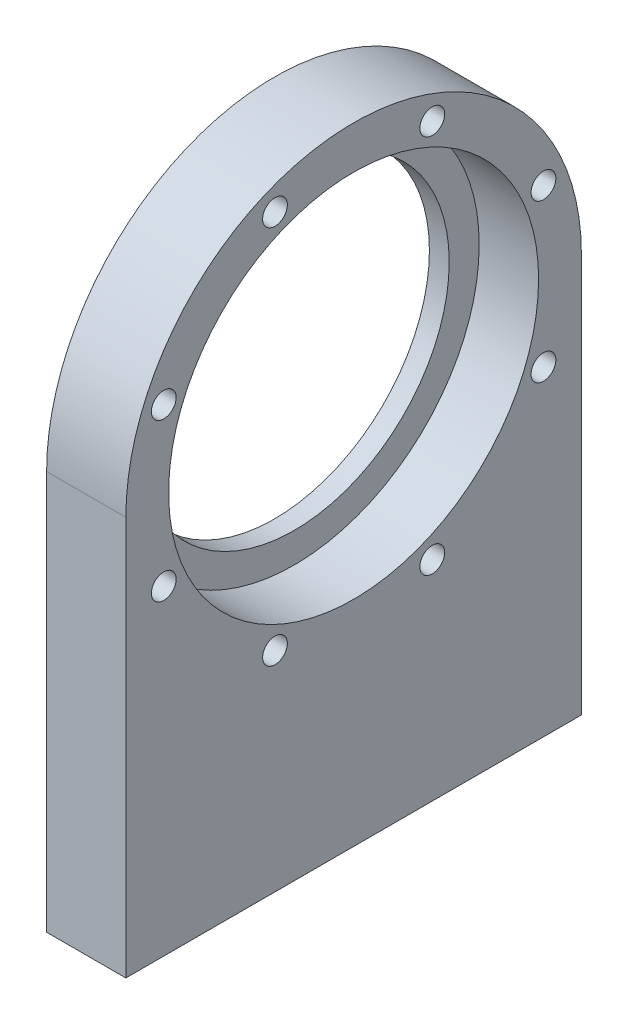
SolidWorks part; units mm, degrees
material "3d打印 35%"
ref_plane "前视基准面" through (0, 0, 0) normal (0, 0, 1) x (1, 0, 0)
ref_plane "上视基准面" through (0, 0, 0) normal (0, 1, 0) x (1, 0, 0)
ref_plane "右视基准面" through (0, 0, 0) normal (1, 0, 0) x (0, 0, -1)
other "Configuration Table"
sketch "草图1" plane through (0, 0, 0) normal (1, 0, 0) x (0, 0, -1)
  line L0 (0, 0) -> (0, 43.0868) construction
  line L1 (0, 0) -> (13.8083, 33.3362) construction
  circle A0 centre (0, 0) radius 23
  circle A1 centre (0, 0) radius 21.6522 construction
  circle A2 centre (0, 0) radius 15.6522
  circle A3 centre (0, 0) radius 18.68
  circle A4 centre (7.9407, 19.1705) radius 1.25
  circle A5 centre (19.1705, 7.9407) radius 1.25
  circle A6 centre (19.1705, -7.9407) radius 1.25
  circle A7 centre (7.9407, -19.1705) radius 1.25
  circle A8 centre (-7.9407, -19.1705) radius 1.25
  circle A9 centre (-19.1705, -7.9407) radius 1.25
  circle A10 centre (-19.1705, 7.9407) radius 1.25
  circle A11 centre (-7.9407, 19.1705) radius 1.25
  point P27 (0, 0)
  dimension "D1" = 8
  dimension "D2" = 46
  dimension "D3" = 2.5
  dimension "D4" = 2.5
  dimension "D5" = 2.5
  dimension "D6" = 20.75
  dimension "D7" = 37.36
  dimension "D8" = 46
extrude "凸台-拉伸2" add sketch "草图1" along normal blind 2 contours A3 A2 region at (0, 0, 18.1516)
extrude "凸台-拉伸3" add sketch "草图1<4>" along normal blind 8 contours A0 A11 A10 A9 A8 A7 A6 A5 A4 A3 region at (0, 0, 22.3495)
sketch "草图1<4>" plane through (0, 0, 0) normal (1, 0, 0) x (0, 0, -1) same geometry as "草图1"
sketch "草图2" plane through (0, 0, 0) normal (-1, 0, 0) x (0, 0, 1)
  line L0 (0, -200000) -> (0, 200043.0868) construction
  line L2 (-23, -40.29) -> (-23, 0)
  line L4 (23, -40.29) -> (23, 0)
  line L5 (-23, -46) -> (23, 0) construction
  line L6 (-23, 0) -> (23, -46) construction
  line L7 (-23, -40.29) -> (23, -40.29)
  circle A0 centre (0, 0) radius 23 construction
  arc A1 (-23, 0) -> (23, 0) centre (0, 0) ccw
  point P0 (0, -23)
extrude "凸台-拉伸4" add sketch "草图2" against normal blind 8
ref_plane "基准面1" through (4, 0, 0) normal (1, 0, 0) x (0, 0, -1)
ref_axis "基准轴1" through (4, -40.29, -23) along (0, 0, 1)
sketch "草图3" plane through (0, -40.29, 0) normal (0, -1, 0) x (1, 0, 0)
  line L0 (4, -25.3) -> (4, 25.3) construction
  line L1 (8, 23) -> (0, 23) construction
  circle A0 centre (4, 19) radius 1.8
  dimension "D1" = 4
extrude "切除-拉伸1" cut sketch "草图3" against normal blind 5
ref_plane "基准面2" through (0, 0, 0) normal (0, 0, -1) x (-1, 0, 0)
mirror "镜向1" about plane through (0, 0, 0) normal (0, 0, -1) of "切除-拉伸1"
